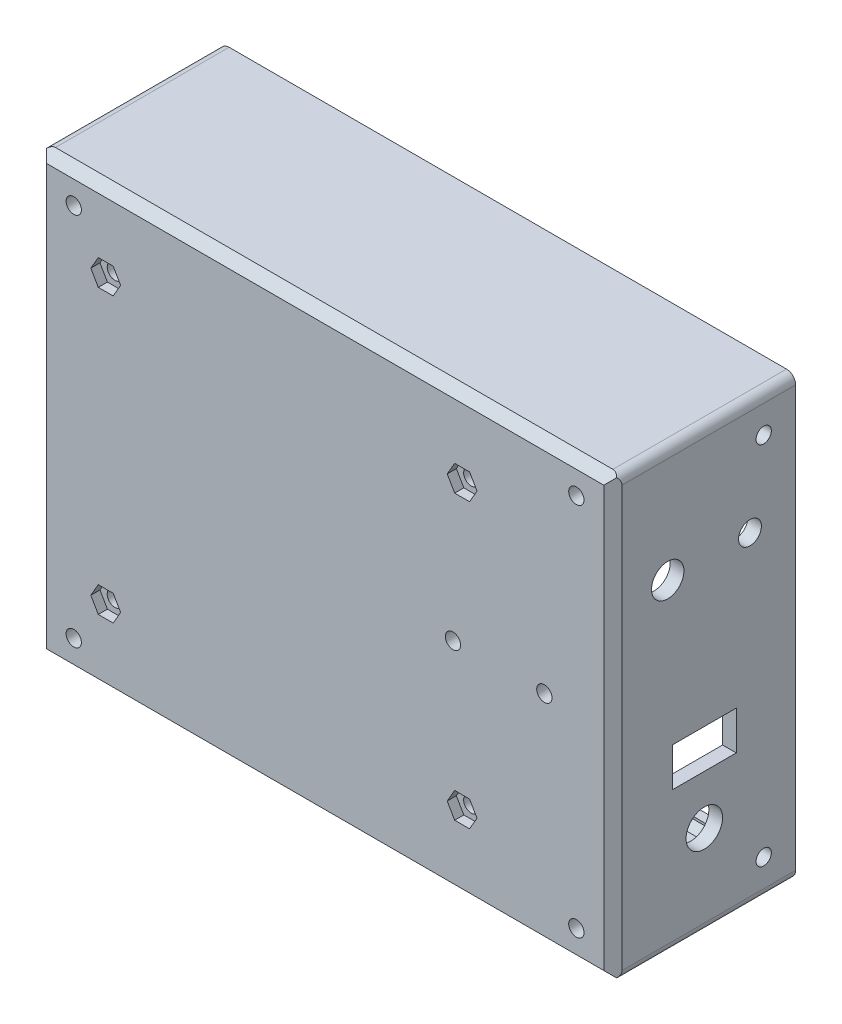
SolidWorks part; units mm, degrees
ref_plane "Front Plane" through (0, 0, 0) normal (0, 0, 1) x (1, 0, 0)
ref_plane "Top Plane" through (0, 0, 0) normal (0, 1, 0) x (1, 0, 0)
ref_plane "Right Plane" through (0, 0, 0) normal (1, 0, 0) x (0, 0, -1)
sketch "Sketch1" plane through (0, 0, 0) normal (0, 0, 1) x (1, 0, 0)
  line L1 (-60, -45) -> (60, -45)
  line L2 (-60, -45) -> (-60, 45)
  line L3 (-60, 45) -> (60, 45)
  line L4 (60, -45) -> (60, 45)
  line L5 (-60, -45) -> (60, 45) construction
  line L6 (-60, 45) -> (60, -45) construction
  line L7 (-48, -31) -> (30, -31)
  line L8 (-48, -31) -> (-48, 31)
  line L9 (-48, 31) -> (30, 31)
  line L10 (30, -31) -> (30, 31)
  line L11 (-48, -31) -> (30, 31) construction
  line L12 (-48, 31) -> (30, -31) construction
  circle A0 centre (-48, 31) radius 1.675
  circle A1 centre (30, 31) radius 1.675
  circle A2 centre (30, -31) radius 1.675
  circle A3 centre (-48, -31) radius 1.675
  circle A4 centre (-55, 41) radius 1.675
  circle A5 centre (55, 41) radius 1.675
  circle A6 centre (55, -41) radius 1.675
  circle A7 centre (-55, -41) radius 1.675
  point P0 (0, 0)
  point P6 (-9, 0)
  dimension "D7" = 3.35
  dimension "D8" = 4
  dimension "D9" = 5
  dimension "D10" = 5
  dimension "D11" = 4
  dimension "D12" = 3.35
  dimension "D13" = 5
  dimension "D14" = 4
  dimension "D15" = 4
  dimension "D16" = 5
  dimension "D1" = 90
  dimension "D2" = 120
  dimension "D3" = 62
  dimension "D4" = 78
  dimension "D5" = 14
  dimension "D6" = 30
extrude "Boss-Extrude2" add sketch "Sketch1" along normal blind 4 contours L1 L4 L3 L2 A3 L8 A0 L9 A1 L10 A2 L7 | A3 L7 A2 L10 A1 L9 A0 L8 region at (-58.5, 0, 0) region at (-9, 0, 0)
sketch "Sketch2" plane through (0, 0, 4) normal (0, 0, 1) x (1, 0, 0)
  line L1 (60, -45) -> (-60, -45)
  line L2 (60, -45) -> (60, 45)
  line L3 (60, 45) -> (-60, 45)
  line L4 (-60, -45) -> (-60, 45)
  line L5 (60, -45) -> (-60, 45) construction
  line L6 (60, 45) -> (-60, -45) construction
  line L7 (63, -48) -> (-63, -48)
  line L8 (63, -48) -> (63, 48)
  line L9 (63, 48) -> (-63, 48)
  line L10 (-63, -48) -> (-63, 48)
  line L11 (63, -48) -> (-63, 48) construction
  line L12 (63, 48) -> (-63, -48) construction
  point P0 (0, 0)
  point P7 (0, 0)
  dimension "D1" = 3
  dimension "D2" = 3
extrude "Boss-Extrude3" add sketch "Sketch2" against normal blind 40
sketch "Sketch3" plane through (-63, 0, 0) normal (-1, 0, 0) x (0, 0, 1)
  line L0 (-36, 48) -> (-36, -48) construction
  line L1 (-36, 48) -> (4, 48) construction
  line L2 (-36, -48) -> (4, -48) construction
  circle A0 centre (-29, -40) radius 1.675
  circle A1 centre (-29, 40) radius 1.675
  dimension "D1" = 3.35
  dimension "D2" = 7
  dimension "D3" = 8
  dimension "D4" = 8
  dimension "D5" = 7
  dimension "D6" = 3.35
extrude "Cut-Extrude1" cut sketch "Sketch3" against normal up to surface (126 mm away) up to face at (63, 0, -16)
sketch "Sketch4" plane through (63, 0, 0) normal (1, 0, 0) x (0, 0, -1)
  line L0 (36, -48) -> (36, 48) construction
  line L9 (9, -17.25) -> (23, -17.25)
  line L10 (9, -17.25) -> (9, -8.75)
  line L11 (9, -8.75) -> (23, -8.75)
  line L12 (23, -17.25) -> (23, -8.75)
  line L13 (9, -17.25) -> (23, -8.75) construction
  line L14 (9, -8.75) -> (23, -17.25) construction
  line L19 (36, -48) -> (-4, -48) construction
  circle A1 centre (16, -28) radius 4
  point P0 (21, 0)
  point P8 (16, -13)
  dimension "D4" = 8
  dimension "D5" = 8.5
  dimension "D6" = 20
  dimension "D7" = 14
  dimension "D2" = 20
  dimension "D3" = 35
  dimension "D10" = 20
extrude "Cut-Extrude3" cut sketch "Sketch4" against normal blind 10
sketch "Sketch5" plane through (63, 0, 0) normal (1, 0, 0) x (0, 0, -1)
  line L0 (36, -48) -> (36, 48) construction
  line L1 (36, 48) -> (-4, 48) construction
  circle A0 centre (8, 23) radius 3.55
  dimension "D1" = 7.1
  dimension "D2" = 28
  dimension "D3" = 25
extrude "Cut-Extrude4" cut sketch "Sketch5" against normal blind 10
sketch "Sketch6" plane through (63, 0, 0) normal (1, 0, 0) x (0, 0, -1)
  line L0 (36, 48) -> (-4, 48) construction
  line L1 (36, -48) -> (36, 48) construction
  circle A0 centre (26, 23) radius 2.5
  point P3 (26, 23)
  dimension "D5" = 5
  dimension "D2" = 10
  dimension "D1" = 25
extrude "Cut-Extrude5" cut sketch "Sketch6" against normal blind 10 contours A0 | A0 region at (63, 23, -26)
sketch "Sketch8" plane through (0, 0, 0) normal (0, 0, -1) x (-1, 0, 0)
  line L1 (-60, -45) -> (-60, 45) construction
  circle A0 centre (-48, 0) radius 1.675
  circle A1 centre (-28, 0) radius 1.675
  circle A2 centre (-30, 31) radius 1.675 construction
  dimension "D1" = 3.35
  dimension "D2" = 3.35
  dimension "D3" = 20
  dimension "D4" = 31
  dimension "D5" = 31
  dimension "D6" = 12
extrude "Cut-Extrude6" cut sketch "Sketch8" against normal blind 10
sketch "Sketch9" plane through (0, 0, 0) normal (0, 0, -1) x (-1, 0, 0)
  line L0 (60, -45) -> (-60, -45) construction
  line L1 (-46.3979, 2.775) -> (-49.6021, 2.775)
  line L2 (-49.6021, 2.775) -> (-51.2043, 0)
  line L3 (-51.2043, 0) -> (-49.6021, -2.775)
  line L4 (-49.6021, -2.775) -> (-46.3979, -2.775)
  line L5 (-46.3979, -2.775) -> (-44.7957, 0)
  line L6 (-44.7957, 0) -> (-46.3979, 2.775)
  line L7 (-26.3979, 2.775) -> (-29.6021, 2.775)
  line L8 (-29.6021, 2.775) -> (-31.2043, 0)
  line L9 (-31.2043, 0) -> (-29.6021, -2.775)
  line L10 (-29.6021, -2.775) -> (-26.3979, -2.775)
  line L11 (-26.3979, -2.775) -> (-24.7957, 0)
  line L12 (-24.7957, 0) -> (-26.3979, 2.775)
  line L13 (-45.2432, 4.775) -> (-50.7568, 4.775)
  line L14 (-50.7568, 4.775) -> (-53.5137, 0)
  line L15 (-53.5137, 0) -> (-50.7568, -4.775)
  line L16 (-50.7568, -4.775) -> (-45.2432, -4.775)
  line L17 (-45.2432, -4.775) -> (-42.4863, 0)
  line L18 (-42.4863, 0) -> (-45.2432, 4.775)
  line L19 (-25.2432, 4.775) -> (-30.7568, 4.775)
  line L20 (-30.7568, 4.775) -> (-33.5137, 0)
  line L21 (-33.5137, 0) -> (-30.7568, -4.775)
  line L22 (-30.7568, -4.775) -> (-25.2432, -4.775)
  line L23 (-25.2432, -4.775) -> (-22.4863, 0)
  line L24 (-22.4863, 0) -> (-25.2432, 4.775)
  line L25 (60, -45) -> (-60, -45) construction
  line L26 (-51.7668, 41) -> (-53.3834, 43.8)
  line L27 (-53.3834, 43.8) -> (-56.6166, 43.8)
  line L28 (-56.6166, 43.8) -> (-58.2332, 41)
  line L29 (-58.2332, 41) -> (-56.6166, 38.2)
  line L30 (-56.6166, 38.2) -> (-53.3834, 38.2)
  line L31 (-53.3834, 38.2) -> (-51.7668, 41)
  line L32 (-50.6121, 41) -> (-52.8061, 44.8)
  line L33 (-52.8061, 44.8) -> (-57.1939, 44.8)
  line L34 (-57.1939, 44.8) -> (-59.3879, 41)
  line L35 (-59.3879, 41) -> (-57.1939, 37.2)
  line L36 (-57.1939, 37.2) -> (-52.8061, 37.2)
  line L37 (-52.8061, 37.2) -> (-50.6121, 41)
  line L38 (58.2332, 41) -> (56.6166, 43.8)
  line L39 (56.6166, 43.8) -> (53.3834, 43.8)
  line L40 (53.3834, 43.8) -> (51.7668, 41)
  line L41 (51.7668, 41) -> (53.3834, 38.2)
  line L42 (53.3834, 38.2) -> (56.6166, 38.2)
  line L43 (56.6166, 38.2) -> (58.2332, 41)
  line L44 (52.8061, 44.8) -> (50.6121, 41)
  line L45 (50.6121, 41) -> (52.8061, 37.2)
  line L46 (52.8061, 37.2) -> (57.1939, 37.2)
  line L47 (57.1939, 37.2) -> (59.3879, 41)
  line L48 (59.3879, 41) -> (57.1939, 44.8)
  line L49 (57.1939, 44.8) -> (52.8061, 44.8)
  line L50 (53.3834, -38.2) -> (51.7668, -41)
  line L51 (51.7668, -41) -> (53.3834, -43.8)
  line L52 (53.3834, -43.8) -> (56.6166, -43.8)
  line L53 (56.6166, -43.8) -> (58.2332, -41)
  line L54 (58.2332, -41) -> (56.6166, -38.2)
  line L55 (56.6166, -38.2) -> (53.3834, -38.2)
  line L56 (50.6121, -41) -> (52.8061, -44.8)
  line L57 (52.8061, -44.8) -> (57.1939, -44.8)
  line L58 (57.1939, -44.8) -> (59.3879, -41)
  line L59 (59.3879, -41) -> (57.1939, -37.2)
  line L60 (57.1939, -37.2) -> (52.8061, -37.2)
  line L61 (52.8061, -37.2) -> (50.6121, -41)
  line L62 (-53.3834, -38.2) -> (-56.6166, -38.2)
  line L63 (-56.6166, -38.2) -> (-58.2332, -41)
  line L64 (-58.2332, -41) -> (-56.6166, -43.8)
  line L65 (-56.6166, -43.8) -> (-53.3834, -43.8)
  line L66 (-53.3834, -43.8) -> (-51.7668, -41)
  line L67 (-51.7668, -41) -> (-53.3834, -38.2)
  line L68 (-52.8061, -37.2) -> (-57.1939, -37.2)
  line L69 (-57.1939, -37.2) -> (-59.3879, -41)
  line L70 (-59.3879, -41) -> (-57.1939, -44.8)
  line L71 (-57.1939, -44.8) -> (-52.8061, -44.8)
  line L72 (-52.8061, -44.8) -> (-50.6121, -41)
  line L73 (-50.6121, -41) -> (-52.8061, -37.2)
  circle A0 centre (-48, 0) radius 2.775 construction
  circle A1 centre (-28, 0) radius 2.775 construction
  circle A2 centre (-48, 0) radius 4.775 construction
  circle A3 centre (-28, 0) radius 4.775 construction
  circle A4 centre (-55, 41) radius 2.8 construction
  circle A5 centre (-55, 41) radius 3.8 construction
  circle A6 centre (55, 41) radius 2.8 construction
  circle A7 centre (55, 41) radius 3.8 construction
  circle A8 centre (55, -41) radius 2.8 construction
  circle A9 centre (55, -41) radius 3.8 construction
  circle A10 centre (-55, -41) radius 2.8 construction
  circle A11 centre (-55, -41) radius 3.8 construction
  dimension "D1" = 5.55
  dimension "D2" = 2
  dimension "D3" = 5.6
  dimension "D4" = 1
extrude "Boss-Extrude4" add sketch "Sketch9" along normal blind 2
sketch "Sketch10" plane through (0, 0, 4) normal (0, 0, 1) x (1, 0, 0)
  line L0 (63, 48) -> (-63, 48) construction
  line L1 (-44.738, 31) -> (-46.369, 33.825)
  line L2 (-46.369, 33.825) -> (-49.631, 33.825)
  line L3 (-49.631, 33.825) -> (-51.262, 31)
  line L4 (-51.262, 31) -> (-49.631, 28.175)
  line L5 (-49.631, 28.175) -> (-46.369, 28.175)
  line L6 (-46.369, 28.175) -> (-44.738, 31)
  line L7 (33.262, 31) -> (31.631, 33.825)
  line L8 (31.631, 33.825) -> (28.369, 33.825)
  line L9 (28.369, 33.825) -> (26.738, 31)
  line L10 (26.738, 31) -> (28.369, 28.175)
  line L11 (28.369, 28.175) -> (31.631, 28.175)
  line L12 (31.631, 28.175) -> (33.262, 31)
  line L25 (-44.738, -31) -> (-46.369, -28.175)
  line L26 (-46.369, -28.175) -> (-49.631, -28.175)
  line L27 (-49.631, -28.175) -> (-51.262, -31)
  line L28 (-51.262, -31) -> (-49.631, -33.825)
  line L29 (-49.631, -33.825) -> (-46.369, -33.825)
  line L30 (-46.369, -33.825) -> (-44.738, -31)
  line L31 (33.262, -31) -> (31.631, -28.175)
  line L32 (31.631, -28.175) -> (28.369, -28.175)
  line L33 (28.369, -28.175) -> (26.738, -31)
  line L34 (26.738, -31) -> (28.369, -33.825)
  line L35 (28.369, -33.825) -> (31.631, -33.825)
  line L36 (31.631, -33.825) -> (33.262, -31)
  circle A0 centre (-48, 31) radius 2.825 construction
  circle A1 centre (30, 31) radius 2.825 construction
  circle A4 centre (-48, -31) radius 2.825 construction
  circle A5 centre (30, -31) radius 2.825 construction
  dimension "D2" = 5.65
extrude "Cut-Extrude8" cut sketch "Sketch10" against normal blind 2
sketch "Sketch12" plane through (0, 0, 0) normal (0, 0, -1) x (-1, 0, 0)
  circle A0 centre (-30, 31) radius 1.675
  circle A1 centre (48, 31) radius 1.675
  circle A2 centre (48, -31) radius 1.675
  circle A3 centre (-30, -31) radius 1.675
  circle A4 centre (-30, -31) radius 4
  circle A5 centre (48, -31) radius 4
  circle A6 centre (48, 31) radius 4
  circle A7 centre (-30, 31) radius 4
  circle A8 centre (-30, 31) radius 1.675 construction
  circle A9 centre (48, 31) radius 1.675 construction
  circle A10 centre (-30, -31) radius 1.675 construction
  circle A11 centre (48, -31) radius 1.675 construction
  dimension "D1" = 8
extrude "Boss-Extrude11" add sketch "Sketch12" along normal blind 3.5
sketch "Sketch16" plane through (0, 0, 0) normal (0, 0, -1) x (-1, 0, 0)
  line L0 (-50.6121, 43) -> (44, 43)
  line L1 (44, 43) -> (44, 30.25)
  line L2 (47.25, 27) -> (58, 27)
  line L3 (58, 27) -> (58, -27)
  line L4 (58, -27) -> (47.25, -27)
  line L5 (44, -30.25) -> (44, -43)
  line L6 (44, -43) -> (-50.6121, -43)
  line L7 (-50.6121, -43) -> (-50.6121, -37.2)
  line L8 (-50.6121, -37.2) -> (-58, -37.2)
  line L9 (-58, -37.2) -> (-58, 37.2)
  line L10 (-58, 37.2) -> (-50.6121, 37.2)
  line L11 (-50.6121, 37.2) -> (-50.6121, 43)
  line L12 (-58, 4.775) -> (-22.4863, 4.775)
  line L13 (-22.4863, 4.775) -> (-22.4863, -4.775)
  line L14 (-22.4863, -4.775) -> (-58, -4.775)
  line L15 (-22.4863, 1) -> (58, 1)
  line L16 (58, 1) -> (58, -1)
  line L17 (58, -1) -> (-22.4863, -1)
  line L18 (-60, 45) -> (-60, -45)
  line L19 (60, -45) -> (-60, -45) construction
  line L20 (-60, -45) -> (-60, 45) construction
  line L21 (-60, -45) -> (60, -45)
  line L22 (60, -45) -> (60, 45)
  line L23 (60, 45) -> (-60, 45)
  line L24 (-1.5, 43) -> (-1.5, -43)
  line L25 (-1.5, -43) -> (0.5, -43)
  line L26 (0.5, -43) -> (0.5, 43)
  line L27 (0.5, 43) -> (-1.5, 43)
  line L28 (-45.2432, 4.775) -> (-50.7568, 4.775) construction
  line L29 (-50.7568, -4.775) -> (-45.2432, -4.775) construction
  line L30 (-60, -45) -> (-60, 45) construction
  line L31 (-52.8061, -37.2) -> (-57.1939, -37.2) construction
  line L32 (-57.1939, 37.2) -> (-52.8061, 37.2) construction
  line L33 (-50.6121, 41) -> (-52.8061, 37.2)
  line L34 (-52.8061, -37.2) -> (-50.6121, -41)
  line L35 (-22.4863, -1) -> (-24.6658, -4.775)
  line L36 (-24.6658, 4.775) -> (-22.4863, 1)
  line L37 (-22.4863, 0) -> (-25.2432, 4.775) construction
  line L38 (-25.2432, -4.775) -> (-22.4863, 0) construction
  circle A0 centre (48, -31) radius 4 construction
  circle A1 centre (48, 31) radius 4 construction
  arc A2 (47.25, -27) -> (44, -30.25) centre (47.25, -30.25) ccw
  arc A3 (44, 30.25) -> (47.25, 27) centre (47.25, 30.25) ccw
  circle M27 centre (-30, -31) radius 4
  line M34 (-45.2432, -4.775) -> (-50.7568, -4.775)
  line M37 (-50.7568, 4.775) -> (-45.2432, 4.775)
  line M40 (-25.2432, -4.775) -> (-30.7568, -4.775)
  line M43 (-30.7568, 4.775) -> (-25.2432, 4.775)
  line M44 (-50.6121, 41) -> (-52.8061, 37.2)
  line M45 (-52.8061, 37.2) -> (-57.1939, 37.2)
  line M54 (52.8061, 37.2) -> (50.6121, 41)
  line M55 (50.6121, 41) -> (52.8061, 44.8)
  line M56 (50.6121, -41) -> (52.8061, -37.2)
  line M61 (52.8061, -44.8) -> (50.6121, -41)
  line M62 (-52.8061, -37.2) -> (-50.6121, -41)
  line M67 (-57.1939, -37.2) -> (-52.8061, -37.2)
  circle M69 centre (-30, 31) radius 4
  dimension "D9" = 3.25
  dimension "D1" = 2
  dimension "D2" = 2
  dimension "D3" = 2
  dimension "D4" = 1
  dimension "D5" = 1.5
  dimension "D6" = 2
  dimension "D7" = 2
  dimension "D8" = 2
extrude "Cut-Extrude11" cut sketch "Sketch16" against normal blind 3 contours L24 L0 L11 L10 L9 L12 L13 L15 M45 M37 M43 M69 | L26 L15 L3 L2 L1 L0 M54 M55 | L26 L6 L5 L4 L3 L17 M61 M56 | L24 L17 L13 L14 L9 L8 L7 L6 M40 M34 M67 M27 | L7 L8 M62 | L10 L11 M44 | L12 L36 L13 | L13 L35 L14 region at (28.5982, 22.6218, 0) region at (51.3434, 38.4667, 0) region at (-27.0447, 20.6782, 0) region at (23.2128, 3.5167, 0) region at (28.5982, -22.6218, 0) region at (-27.0447, -20.6782, 0) region at (23.2128, -3.5167, 0) region at (51.3434, -38.4667, 0)
sketch "Sketch17" plane through (0, 45, 0) normal (0, -1, 0) x (1, 0, 0)
  line L1 (-58, -34) -> (57, -34)
  line L2 (-58, -34) -> (-58, -2)
  line L3 (-58, -2) -> (57, -2)
  line L4 (57, -34) -> (57, -2)
  line L5 (-60, 0) -> (60, 0) construction
  line L6 (60, -36) -> (60, 0) construction
  line L7 (-60, -36) -> (-60, 0) construction
  line L8 (60, -36) -> (-60, -36) construction
  line L9 (-0.5, 3) -> (-0.5, 0) construction
  line L10 (-58, -17) -> (57, -17)
  line L11 (-58, -17) -> (-58, -19)
  line L12 (-58, -19) -> (57, -19)
  line L13 (57, -17) -> (57, -19)
  line L14 (-0.5, -2) -> (1.5, -2)
  line L15 (-0.5, -2) -> (-0.5, -34)
  line L16 (-0.5, -34) -> (1.5, -34)
  line L17 (1.5, -2) -> (1.5, -34)
  dimension "D1" = 2
  dimension "D2" = 3
  dimension "D3" = 2
  dimension "D4" = 2
  dimension "D5" = 2
  dimension "D6" = 2
  dimension "D7" = 15
extrude "Cut-Extrude13" cut sketch "Sketch17" against normal blind 2 contours L15 L12 L2 L1 | L15 L3 L2 L10 | L3 L17 L10 L4 | L12 L17 L1 L4 region at (-29.25, 45, -26.5) region at (29.25, 45, -26.5) region at (-29.25, 45, -9.5) region at (29.25, 45, -9.5)
sketch "Sketch20" plane through (0, -45, 0) normal (0, 1, 0) x (1, 0, 0)
  line L0 (-58, -3) -> (-58, 0) construction
  line L1 (-58, 34) -> (58, 34)
  line L2 (-58, 34) -> (-58, 2)
  line L3 (-58, 2) -> (58, 2)
  line L4 (58, 34) -> (58, 2)
  line L5 (-0.5, 34) -> (1.5, 34)
  line L6 (-0.5, 34) -> (-0.5, 2)
  line L7 (-0.5, 2) -> (1.5, 2)
  line L8 (1.5, 34) -> (1.5, 2)
  line L9 (-58, 19) -> (58, 19)
  line L10 (-58, 19) -> (-58, 17)
  line L11 (-58, 17) -> (58, 17)
  line L12 (58, 19) -> (58, 17)
  line L13 (58, -3) -> (58, 0) construction
  line L15 (-60, 36) -> (60, 36) construction
  line L16 (-58, 19) -> (-0.5, 19) construction
  line L17 (-58, 2) -> (-0.5, 2) construction
  line L18 (1.5, 19) -> (57, 19) construction
  line L20 (-0.5, 2) -> (-0.5, 17) construction
  dimension "D1" = 2
  dimension "D2" = 2
  dimension "D3" = 2
extrude "Cut-Extrude14" cut sketch "Sketch20" against normal blind 2 contours L2 L9 L6 L1 | L8 L9 L4 L1 | L11 L8 L3 L4 | L11 L2 L3 L6 region at (-29.25, -45, -26.5) region at (29.75, -45, -26.5) region at (-29.25, -45, -9.5) region at (29.75, -45, -9.5)
sketch "Sketch21" plane through (-60, 0, 0) normal (1, 0, 0) x (0, 0, -1)
  line L0 (0, -45) -> (0, 45) construction
  line L1 (26, 43) -> (2, 43)
  line L2 (26, 43) -> (26, -43)
  line L3 (26, -43) -> (2, -43)
  line L4 (2, 43) -> (2, -43)
  line L5 (26, 37) -> (34, 37)
  line L6 (26, 37) -> (26, -37)
  line L7 (26, -37) -> (34, -37)
  line L8 (34, 37) -> (34, -37)
  line L9 (2, 1) -> (34, 1)
  line L10 (2, 1) -> (2, -1)
  line L11 (2, -1) -> (34, -1)
  line L12 (34, 1) -> (34, -1)
  line L13 (19, 43) -> (17, 43)
  line L14 (19, 43) -> (19, -43)
  line L15 (19, -43) -> (17, -43)
  line L16 (17, 43) -> (17, -43)
  line L17 (36, 45) -> (0, 45) construction
  line L18 (36, 45) -> (36, -45) construction
  line L19 (36, -45) -> (0, -45) construction
  line L20 (-3, -1) -> (0, -1) construction
  dimension "D1" = 2
  dimension "D2" = 2
  dimension "D3" = 2
  dimension "D4" = 2
  dimension "D5" = 6
  dimension "D6" = 6
  dimension "D7" = 8
  dimension "D8" = 2
  dimension "D9" = 2
  dimension "D10" = 15
extrude "Cut-Extrude15" cut sketch "Sketch21" against normal blind 2 contours L2 L9 L8 L5 | L1 L14 L9 L2 | L11 L2 L7 L8 | L11 L14 L3 L2 | L16 L11 L4 L3 | L16 L1 L4 L9 region at (-60, 22, -22.5) region at (-60, 19, -30) region at (-60, 22, -9.5) region at (-60, -22, -22.5) region at (-60, -19, -30) region at (-60, -22, -9.5)
chamfer "Chamfer6" distance 1.5 angle 45 14 edges at (29.75, -47, -17) (29.75, -47, -34) (-29.25, -47, -34) (-29.25, -47, -17) (-62, 22, -17) (-62, -22, -17) (-62, 40, -26) (-62, -19, -34) (-62, -40, -26) (-62, 19, -34) (-29.25, 47, -17) (29.25, 47, -17) (-29.25, 47, -34) (29.25, 47, -34)
chamfer "Chamfer7" distance 2 angle 45 4 edges at (-63, 0, 4) (0, 48, 4) (63, 0, 4) (0, -48, 4)
fillet "Fillet1" radius 2 4 edges at (-63, -48, -17) (-63, 48, -17) (63, 48, -17) (63, -48, -17)
sketch "Sketch22" plane through (60, 0, 0) normal (-1, 0, 0) x (0, 0, 1)
  line L1 (-3, 16.95) -> (-13, 16.95)
  line L2 (-3, 16.95) -> (-3, 29.05)
  line L3 (-3, 29.05) -> (-13, 29.05)
  line L4 (-13, 16.95) -> (-13, 29.05)
  line L5 (-3, 16.95) -> (-13, 29.05) construction
  line L6 (-3, 29.05) -> (-13, 16.95) construction
  line L7 (-13, 29.05) -> (-3, 29.05)
  line L8 (-13, 29.05) -> (-13, 31.05)
  line L9 (-13, 31.05) -> (-3, 31.05)
  line L10 (-3, 29.05) -> (-3, 31.05)
  line L11 (-3, 16.95) -> (-13, 16.95)
  line L12 (-3, 16.95) -> (-3, 14.95)
  line L13 (-3, 14.95) -> (-13, 14.95)
  line L14 (-13, 16.95) -> (-13, 14.95)
  point P0 (-8, 23)
  dimension "D1" = 2
  dimension "D2" = 2
  dimension "D3" = 10
  dimension "D4" = 12.1
extrude "Boss-Extrude12" add sketch "Sketch22" along normal blind 2 contours L3 L10 L9 L8 | L1 L14 L13 L12 region at (60, 15.95, -8) region at (60, 30.05, -8)
chamfer "Chamfer8" distance 2 angle 45 2 edges at (58, 30.05, -3) (58, 15.95, -3)
